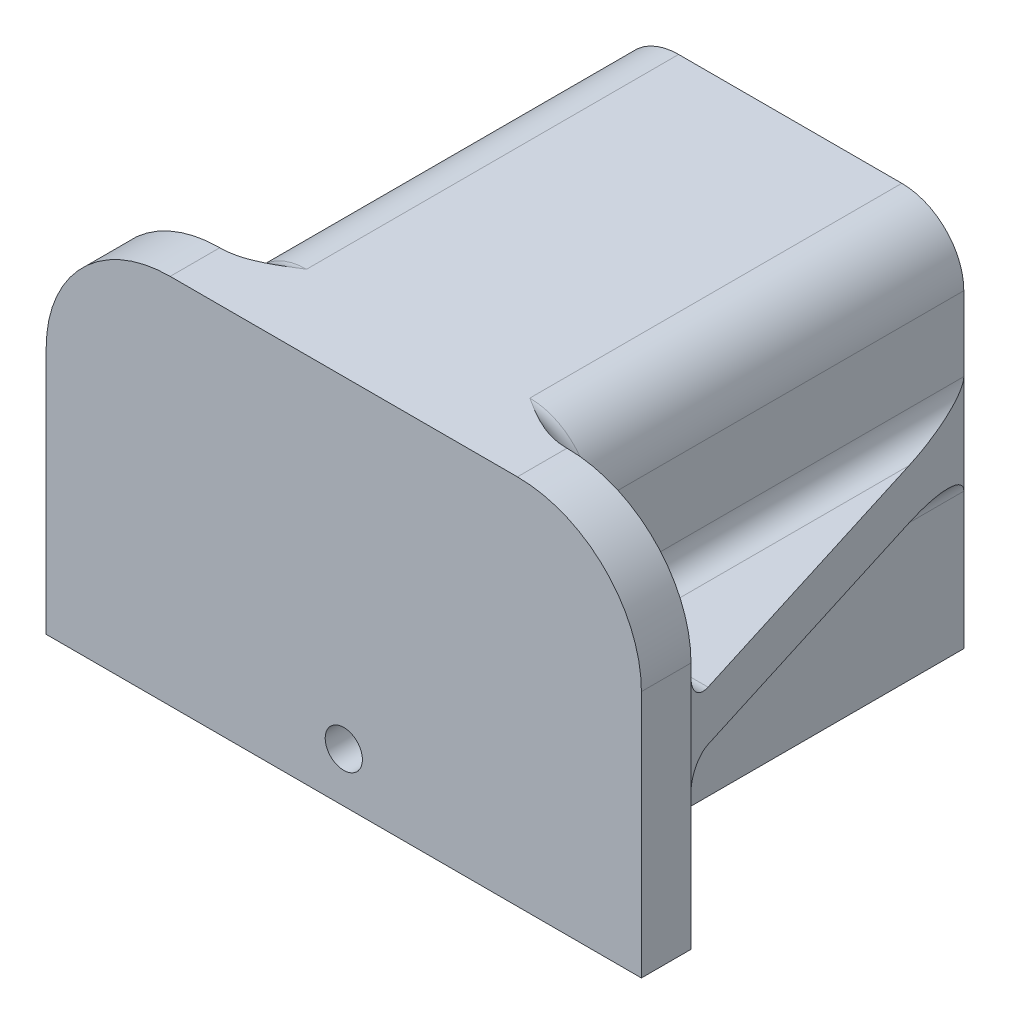
SolidWorks part; units mm, degrees
material "ABS"
ref_plane "Front Plane" through (0, 0, 0) normal (0, 0, 1) x (1, 0, 0)
ref_plane "Top Plane" through (0, 0, 0) normal (0, 1, 0) x (1, 0, 0)
ref_plane "Right Plane" through (0, 0, 0) normal (1, 0, 0) x (0, 0, -1)
sketch "Sketch1" plane through (0, 0, 0) normal (0, 1, 0) x (1, 0, 0)
  line L0 (0, 0) -> (0, -6) construction
  line L1 (10, 0) -> (-10, 0)
  line L2 (-10, 0) -> (-10, 30)
  line L3 (-10, 30) -> (-14, 30)
  line L4 (-24, -6) -> (-24, -2)
  line L5 (-24, -6) -> (24, -6)
  line L7 (-14, -2) -> (-14, 30)
  line L8 (-24, -2) -> (-14, -2)
  line L9 (24, -2) -> (14, -2)
  line L10 (14, -2) -> (14, 30)
  line L12 (24, -6) -> (24, -2)
  line L13 (10, 30) -> (14, 30)
  line L14 (10, 0) -> (10, 30)
  dimension "D1" = 10
  dimension "D2" = 30
  dimension "D3" = 6
  dimension "D4" = 4
  dimension "D5" = 10
  dimension "D6" = 4
extrude "Boss-Extrude1" add sketch "Sketch1" along normal mid plane 30
sketch "Sketch2" plane through (0, 0, 0) normal (0, 1, 0) x (1, 0, 0)
  line L0 (14, 30) -> (14, -2)
  line L1 (14, -2) -> (24, -2)
  line L2 (24, -2) -> (14, 30)
  point P3 (14.4577, 29.6016)
  point P4 (14.0578, 27.2123)
  point P6 (0, 0)
  point P8 (0, 0)
extrude "Boss-Extrude2" add sketch "Sketch2" along normal mid plane 4
mirror "Mirror1" about plane through (0, 0, 0) normal (1, 0, 0) of "Boss-Extrude2"
sketch "Sketch3" plane through (0, 0, 0) normal (0, 0, -1) x (-1, 0, 0)
  line L0 (0, 0) -> (0, -11) construction
  line L1 (0, -11) -> (0, -15) construction
  line L2 (-10, -15) -> (10, -15) construction
  circle A0 centre (0, -11) radius 1.5
  dimension "D2" = 3
  dimension "D1" = 4
extrude "Cut-Extrude1" cut sketch "Sketch3" against normal through all
fillet "Fillet1" radius 10 2 edges at (24, 15, 4) (-24, 15, 4)
sketch "Sketch4" plane through (0, 0, 0) normal (0, 0, -1) x (-1, 0, 0)
  line L0 (0, -15) -> (4, -15)
  line L1 (-10, -15) -> (10, -15) construction
  line L2 (4, -15) -> (4, -11)
  line L3 (0, -15) -> (-4, -15)
  line L4 (-4, -15) -> (-4, -11)
  circle A0 centre (0, -11) radius 4 construction
  arc A1 (4, -11) -> (-4, -11) centre (0, -11) ccw
  point P11 (0, 0)
  dimension "D1" = 8
extrude "Cut-Extrude4" cut sketch "Sketch4" against normal blind 2
fillet "Fillet2" radius 0.5 3 edges at (-4, -13, 2) (4, -13, 2) (0, -7, 2)
sketch "Sketch5" plane through (0, 0, 0) normal (0, 0, -1) x (-1, 0, 0)
  line L0 (-10, 15) -> (-10, -15) construction
  line L3 (10, 15) -> (-10, 15)
  line L7 (10, 15) -> (10, 11)
  line L8 (10, 11) -> (-10, 11)
  line L9 (-10, 15) -> (-10, 11)
  dimension "D1" = 4
extrude "Boss-Extrude3" add sketch "Sketch5" along normal up to surface (30 mm away) up to face at (-12.6667, 0, -30)
fillet "Fillet3" radius 5 5 edges at (0, 11, 0) (-10, 11, -15) (10, 11, -15) (-14, 15, -14) (14, 15, -14)
fillet "Fillet4" radius 2 14 edges at (-12.5355, 13.5355, 2) (12.5355, 13.5355, 2) (-14, -2, -14) (-19, -2, 2) (-19, 2, 2) (-14, 2, -14) (-14, 6, 2) (-14, -8.5, 2) (14, 6, 2) (14, -8.5, 2) (14, -2, -14) (19, -2, 2) (19, 2, 2) (14, 2, -14)
